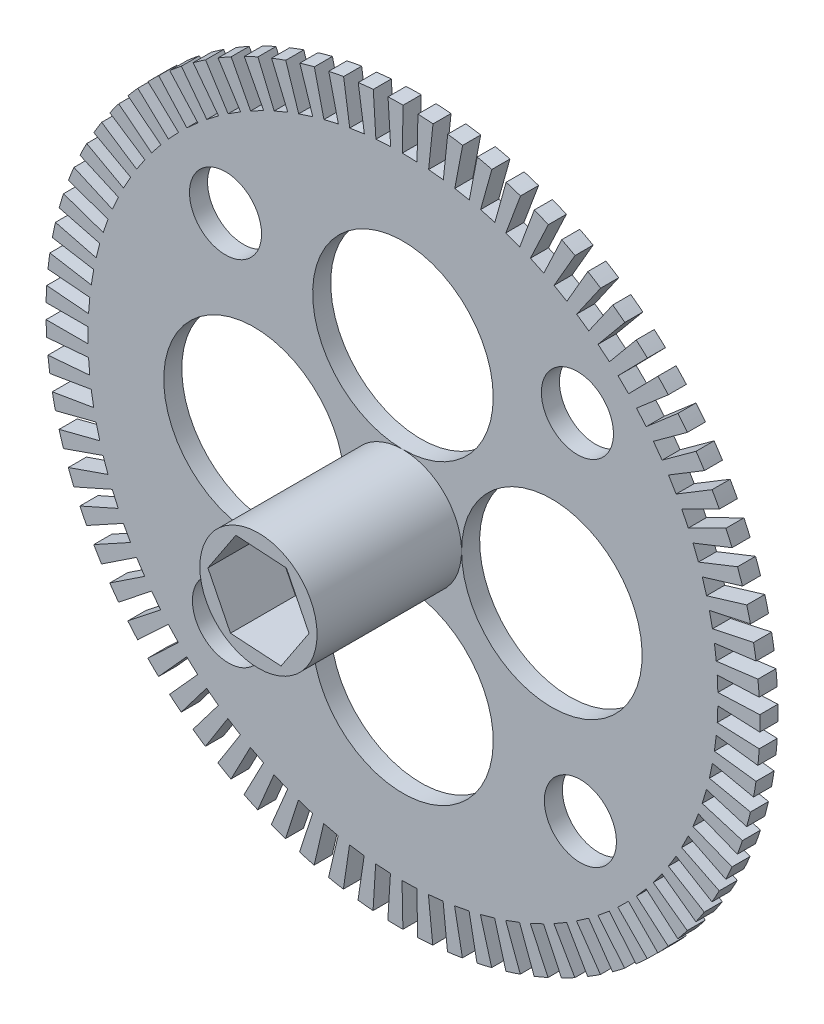
SolidWorks part; units mm, degrees
ref_plane "Front Plane" through (0, 0, 0) normal (0, 0, 1) x (1, 0, 0)
ref_plane "Top Plane" through (0, 0, 0) normal (0, 1, 0) x (1, 0, 0)
ref_plane "Right Plane" through (0, 0, 0) normal (1, 0, 0) x (0, 0, -1)
sketch "Sketch1" plane through (0, 0, 0) normal (0, 0, 1) x (1, 0, 0)
  line L0 (0, 0) -> (-50, 0)
  circle A0 centre (0, 0) radius 50
extrude "Boss-Extrude1" add sketch "Sketch1" along normal blind 2.5 contours A0 region at (0, -48.5858, 0)
sketch "Sketch9" plane through (0, 0, 2.5) normal (0, 0, 1) x (1, 0, 0)
  line L1 (-49.7085, 1.0399) -> (-43.5892, 1.0399)
  line L2 (-49.7085, 1.0399) -> (-49.7085, -1.009)
  line L3 (-49.9892, 1.0399) -> (-43.5892, 1.0399)
  line L4 (-49.9892, 1.0399) -> (-49.9892, -1.009)
  line L5 (-49.9892, -1.009) -> (-43.5892, -1.009)
  line L6 (-43.5892, 1.0399) -> (-43.5892, -1.009)
  line L7 (-49.7085, -1.009) -> (-43.5892, -1.009)
  line L8 (-43.5892, 1.0399) -> (-43.5892, -1.009)
  circle A0 centre (0, 0) radius 50 construction
  dimension "D1" = 6.4
extrude "Cut-Extrude9" cut sketch "Sketch9" against normal blind 2.5 contours L6 L1 L2 L5 region at (-46.6489, 0.0155, 2.5)
pattern_circular "CirPattern6" count 75 over 360 about axis through (0, 0, 2.5) along (0, 0, 1) of "Cut-Extrude9"
sketch "Sketch12" plane through (0, 0, 2.5) normal (0, 0, 1) x (1, 0, 0)
  circle A0 centre (0, 0) radius 49.7188
  circle A1 centre (0, 0) radius 49.4104
  circle A2 centre (0, 0) radius 50.309
extrude "Cut-Extrude10" cut sketch "Sketch12" against normal blind 2.5 contours A2 A0 | A0 A1 region at (-49.5781, 0, 2.5) region at (-50.1667, 0, 2.5)
sketch "Sketch14" plane through (0, 0, 2.5) normal (0, 0, 1) x (1, 0, 0)
  circle A0 centre (0, 20.6134) radius 12.4985
extrude "Cut-Extrude11" cut sketch "Sketch14" against normal blind 2.5
pattern_circular "CirPattern7" count 4 over 360 about axis through (0, 0, 2.5) along (0, 0, 1) of "Cut-Extrude11"
sketch "Sketch15" plane through (0, 0, 2.5) normal (0, 0, 1) x (1, 0, 0)
  circle A0 centre (-24.5627, 24.1543) radius 4.9883
extrude "Cut-Extrude12" cut sketch "Sketch15" against normal blind 2.5
pattern_circular "CirPattern8" count 4 over 360 about axis through (0, 0, 2.5) along (0, 0, 1) of "Cut-Extrude12"
sketch "Sketch16" plane through (0, 0, 2.5) normal (0, 0, 1) x (1, 0, 0)
  circle A0 centre (0, 0) radius 8.115
extrude "Boss-Extrude2" add sketch "Sketch16" along normal blind 20
sketch "Sketch17" plane through (0, 0, 22.5) normal (0, 0, 1) x (1, 0, 0)
  circle A0 centre (0, 0) radius 5.2326
extrude "Cut-Extrude13" cut sketch "Sketch17" against normal blind 50
sketch "Sketch18" plane through (0, 0, 22.5) normal (0, 0, 1) x (1, 0, 0)
  circle A0 centre (0, 0) radius 5.2326
extrude "Boss-Extrude3" add sketch "Sketch18" against normal blind 23
sketch "Sketch19" plane through (0, 0, 22.5) normal (0, 0, 1) x (1, 0, 0)
  line L1 (-3.1271, 6.2775) -> (-7, 0.4306)
  line L2 (-7, 0.4306) -> (-3.8729, -5.8469)
  line L3 (-3.8729, -5.8469) -> (3.1271, -6.2775)
  line L4 (3.1271, -6.2775) -> (7, -0.4306)
  line L5 (7, -0.4306) -> (3.8729, 5.8469)
  line L6 (3.8729, 5.8469) -> (-3.1271, 6.2775)
  circle A0 centre (0, 0) radius 6.0736 construction
  dimension "D1" = 7
extrude "Cut-Extrude14" cut sketch "Sketch19" against normal blind 9
sketch "Sketch20" plane through (0, 0, -0.5) normal (0, 0, -1) x (-1, 0, 0)
  line L1 (1.5747, 6.8206) -> (-5.1194, 4.774)
  line L2 (-5.1194, 4.774) -> (-6.6942, -2.0465)
  line L3 (-6.6942, -2.0465) -> (-1.5747, -6.8206)
  line L4 (-1.5747, -6.8206) -> (5.1194, -4.774)
  line L5 (5.1194, -4.774) -> (6.6942, 2.0465)
  line L6 (6.6942, 2.0465) -> (1.5747, 6.8206)
  circle A0 centre (0, 0) radius 6.0622 construction
  dimension "D1" = 7
extrude "Cut-Extrude15" cut sketch "Sketch20" against normal blind 9
